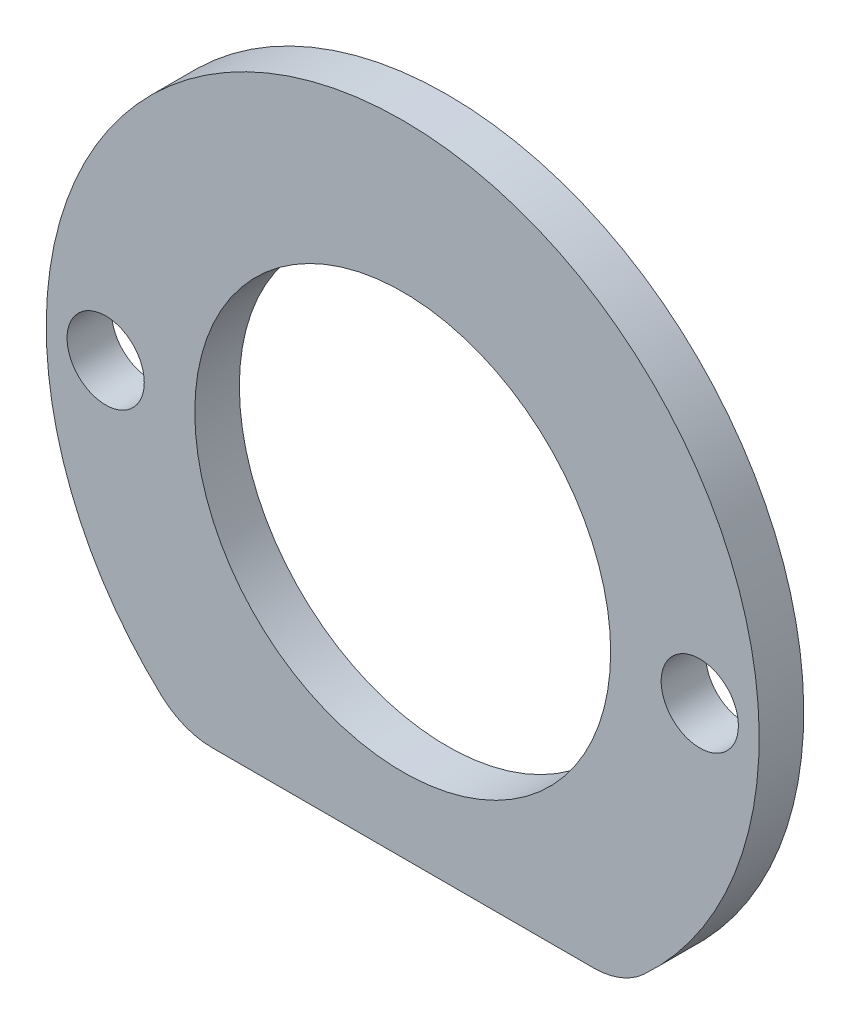
SolidWorks part; units mm, degrees
material "Gerais  - 6061-T6"
ref_plane "Plano frontal" through (0, 0, 0) normal (0, 0, 1) x (1, 0, 0)
ref_plane "Plano superior" through (0, 0, 0) normal (0, 1, 0) x (1, 0, 0)
ref_plane "Plano direito" through (0, 0, 0) normal (1, 0, 0) x (0, 0, -1)
sketch "Esboço1" plane through (0, 0, 0) normal (0, 0, 1) x (1, 0, 0)
  line L0 (-20, 0) -> (20, 0) construction
  line L1 (14.6629, -19) -> (-14.6629, -19)
  line L2 (0, -19) -> (0, -14) construction
  line L4 (0, 0) -> (0, -24) construction
  circle A0 centre (0, 0) radius 14
  circle A1 centre (0, 0) radius 24
  circle A2 centre (-20, 0) radius 2.6
  circle A3 centre (20, 0) radius 2.6
  point P12 (20.7472, -2.4903)
  dimension "D1" = 28
  dimension "D2" = 48
  dimension "D3" = 40
  dimension "D4" = 5.2
  dimension "D5" = 5
extrude "Ressalto-extrusão1" add sketch "Esboço1" along normal blind 3 contours L1 A1 A3 A2 A0 region at (0, -18.3556, 0)
fillet "Filete1" radius 5 2 edges at (-14.6629, -19, 1.5) (14.6629, -19, 1.5)
